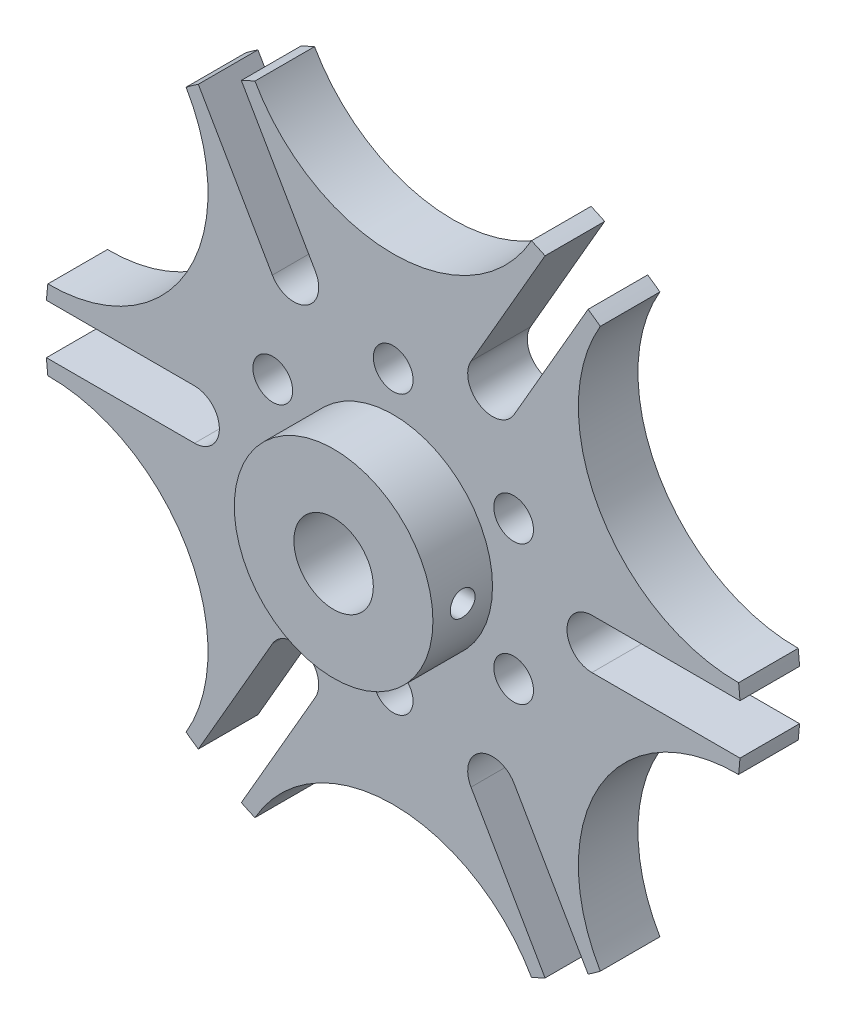
SolidWorks part; units mm, degrees
ref_plane "前视基准面" through (0, 0, 0) normal (0, 0, 1) x (1, 0, 0)
ref_plane "上视基准面" through (0, 0, 0) normal (0, 1, 0) x (1, 0, 0)
ref_plane "右视基准面" through (0, 0, 0) normal (1, 0, 0) x (0, 0, -1)
sketch "草图1" plane through (0, 0, 0) normal (0, 0, 1) x (1, 0, 0)
  circle A0 centre (0, 0) radius 70
extrude "凸台-拉伸1" add sketch "草图1" along normal blind 12
ref_plane "基准面1" through (0, 0, 12) normal (0, 0, 1) x (1, 0, 0)
sketch "草图2" plane through (0, 0, 12) normal (0, 0, 1) x (1, 0, 0)
  circle A0 centre (0, 0) radius 20
extrude "凸台-拉伸2" add sketch "草图2" along normal blind 12
sketch "草图3" plane through (0, 0, 0) normal (0, 0, 1) x (1, 0, 0)
  circle A0 centre (0, 0) radius 8
extrude "切除-拉伸1" cut sketch "草图3" along normal through all
sketch "草图4" plane through (0, 0, 0) normal (0, 0, 1) x (1, 0, 0)
  line L0 (75, -5) -> (40, -5)
  line L1 (40, 5) -> (75, 5)
  line L2 (75, 5) -> (75, -5)
  arc A0 (40, -5) -> (40, 5) centre (40, 0) cw
extrude "切除-拉伸2" cut sketch "草图4" along normal through all
ref_axis "基准轴1" through (0, 0, 25.2) along (0, 0, -1)
pattern_circular "阵列(圆周)1" count 6 over 360 about axis through (0, 0, 25.2) along (0, 0, -1) of "切除-拉伸2"
sketch "草图5" plane through (0, 0, 0) normal (0, 0, 1) x (1, 0, 0)
  circle A0 centre (69.282, 40) radius 32
extrude "切除-拉伸3" cut sketch "草图5" against normal mid plane 282
pattern_circular "阵列(圆周)2" count 6 over 360 about axis through (0, 0, 25.2) along (0, 0, -1) of "切除-拉伸3"
sketch "草图6" plane through (0, 0, 0) normal (0, 0, 1) x (1, 0, 0)
  circle A0 centre (24.2487, 14) radius 4
  circle A1 centre (0, 28) radius 4
  circle A2 centre (-24.2487, 14) radius 4
  circle A3 centre (-24.2487, -14) radius 4
  circle A4 centre (0, -28) radius 4
  circle A5 centre (24.2487, -14) radius 4
extrude "切除-拉伸4" cut sketch "草图6" against normal mid plane 281.284
ref_plane "基准面2" through (25, 0, 0) normal (1, 0, 0) x (0, 0, -1)
ref_plane "基准面3" through (20, 0, 0) normal (1, 0, 0) x (0, 0, -1)
sketch "草图8" plane through (20, 0, 0) normal (1, 0, 0) x (0, 0, -1)
  circle A0 centre (-18, 0) radius 2.5
extrude "切除-拉伸7" cut sketch "草图8" against normal blind 13
